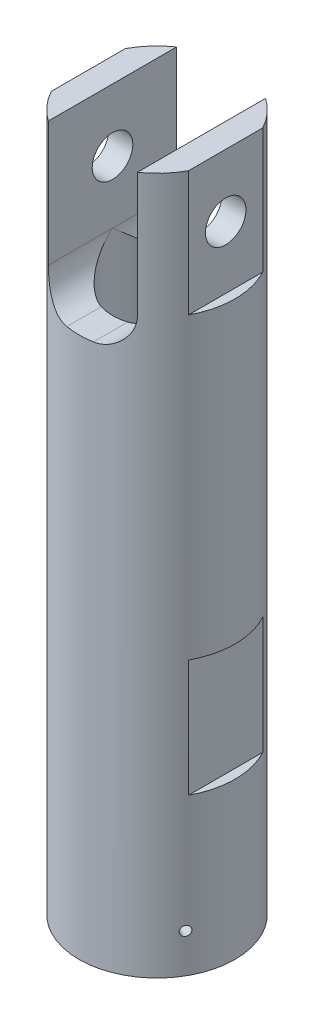
SolidWorks part; units mm, degrees
material "6061-T6 (SS)"
ref_plane "Front Plane" through (0, 0, 0) normal (0, 0, 1) x (1, 0, 0)
ref_plane "Top Plane" through (0, 0, 0) normal (0, 1, 0) x (1, 0, 0)
ref_plane "Right Plane" through (0, 0, 0) normal (1, 0, 0) x (0, 0, -1)
sketch "Sketch1" plane through (0, 0, 0) normal (0, 1, 0) x (1, 0, 0)
  circle A0 centre (0, 0) radius 4.826
  circle A1 centre (0, 0) radius 12.7
  dimension "D1" = 9.652
  dimension "D2" = 25.4
extrude "Socket Head Stop" add sketch "Sketch1" along normal blind 5.08
sketch "Sketch2" plane through (0, 0, 0) normal (0, 1, 0) x (1, 0, 0)
  circle A0 centre (0, 0) radius 12.7 construction
  circle A1 centre (0, 0) radius 12.7
  circle A2 centre (0, 0) radius 7.239
  dimension "D1" = 14.478
extrude "Main Body" add sketch "Sketch2" along normal blind 100.7072
sketch "Sketch6" plane through (0, 0, 0) normal (1, 0, 0) x (0, 0, -1)
  line L0 (-12.7, 0) -> (12.7, 0) construction
  circle A0 centre (0, 90.5472) radius 3.302
  dimension "D2" = 6.604
  dimension "D1" = 90.5472
extrude "Rod End Mounting Holes" cut sketch "Sketch6" against normal through all both and the other way through all
sketch "Sketch3" plane through (0, 0, 0) normal (0, 0, 1) x (1, 0, 0)
  line L0 (-7.239, 100.7072) -> (-7.239, 80.3872)
  line L1 (7.239, 100.7072) -> (-7.239, 100.7072) construction
  line L2 (-2.159, 75.3072) -> (2.159, 75.3072)
  line L3 (7.239, 100.7072) -> (7.239, 80.3872)
  line L4 (12.7, 100.7072) -> (-12.7, 100.7072) construction
  line L5 (12.7, 100.7072) -> (-12.7, 100.7072)
  line L6 (-12.7, 0) -> (12.7, 0) construction
  line L7 (7.239, 100.7072) -> (-7.239, 100.7072)
  line L8 (-12.7, 100.7072) -> (-12.7, 93.8492) construction
  line L9 (-12.7, 100.7072) -> (-11.176, 100.7072)
  line L10 (-12.7, 100.7072) -> (-12.7, 80.3872)
  line L11 (-12.7, 80.3872) -> (-11.176, 80.3872)
  line L12 (-11.176, 100.7072) -> (-11.176, 80.3872)
  line L13 (12.7, 93.8492) -> (12.7, 100.7072) construction
  line L14 (12.7, 100.7072) -> (11.176, 100.7072)
  line L15 (12.7, 100.7072) -> (12.7, 80.3872)
  line L16 (12.7, 80.3872) -> (11.176, 80.3872)
  line L17 (11.176, 100.7072) -> (11.176, 80.3872)
  line L18 (12.7, 0) -> (12.7, 87.2452) construction
  line L19 (12.7, 31.75) -> (11.176, 31.75)
  line L20 (12.7, 31.75) -> (12.7, 12.7)
  line L21 (12.7, 12.7) -> (11.176, 12.7)
  line L22 (11.176, 31.75) -> (11.176, 12.7)
  line L23 (-12.7, 87.2452) -> (-12.7, 0) construction
  line L24 (-12.7, 31.75) -> (-11.176, 31.75)
  line L25 (-12.7, 31.75) -> (-12.7, 12.7)
  line L26 (-12.7, 12.7) -> (-11.176, 12.7)
  line L27 (-11.176, 31.75) -> (-11.176, 12.7)
  arc A0 (-7.239, 80.3872) -> (-2.159, 75.3072) centre (-2.159, 80.3872) ccw
  arc A1 (7.239, 80.3872) -> (2.159, 75.3072) centre (2.159, 80.3872) cw
  point P6 (0, 75.3072)
  point P13 (0, 100.7072)
  point P14 (-7.239, 90.5472)
  point P39 (-11.176, 90.5472)
  point P43 (11.176, 90.5472)
  dimension "D3" = 5.08
  dimension "D1" = 14.478
  dimension "D2" = 90.5472
  dimension "D4" = 1.524
  dimension "D5" = 19.05
  dimension "D6" = 12.7
extrude "Rod End Body Holes And Wrench Cuts" cut sketch "Sketch3" against normal through all both and the other way through all contours A1 L3 L5 L0 A0 L2 | L19 L22 L21 L20 | L10 L11 L12 L5 | L5 L17 L16 L15 | L27 L26 L25 L24 region at (0, 88.3663, 0) region at (11.938, 90.5472, 0) region at (-11.938, 90.5472, 0) region at (11.938, 22.225, 0)
sketch "Sketch4" plane through (0, 0, 0) normal (0, -1, 0) x (1, 0, 0)
  circle A0 centre (0, 0) radius 12.7 construction
  circle A1 centre (0, 0) radius 12.7
  circle A2 centre (0, 0) radius 10.414
  dimension "D1" = 20.828
extrude "Rack Cover" add sketch "Sketch4" along normal blind 12.7
ref_axis "Safety Wire Axis" through (0, -18.5609, 0) along (0, 1, 0)
ref_plane "Safety Wire Plane" through (0, 0, 0) normal (0.866, 0, 0.5) x (0, 1, 0)
sketch "Sketch7" plane through (0, 0, 0) normal (0.866, 0, 0.5) x (0, 1, 0)
  line L0 (-18.5609, 0) -> (110.378, 0) construction
  line L2 (0, 10.414) -> (0, -10.414) construction
  circle A0 centre (-6.35, 0) radius 0.762
  dimension "D1" = 1.524
  dimension "D2" = 6.35
extrude "Safety Wire Holes" cut sketch "Sketch7" against normal through all both and the other way through all
sketch3d "Steering Link Mount"
  line L0 (11.176, 90.5472, 0) -> (-11.176, 90.5472, 0) construction
  circle A0 centre (11.176, 90.5472, 0) radius 3.302 construction
  point P4 (14.478, 90.5472, 0)
  point P5 (0, 90.5472, 0)
